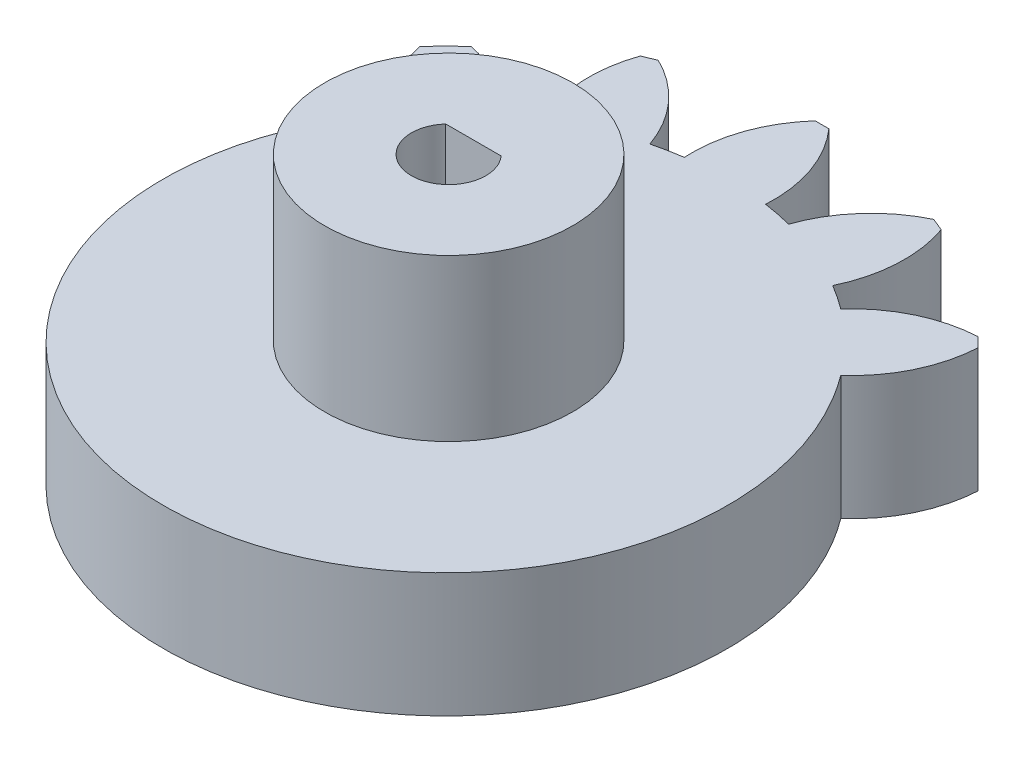
SolidWorks part; units mm, degrees
material "3D printed plastic"
ref_plane "Front Plane" through (0, 0, 0) normal (0, 0, 1) x (1, 0, 0)
ref_plane "Top Plane" through (0, 0, 0) normal (0, 1, 0) x (1, 0, 0)
ref_plane "Right Plane" through (0, 0, 0) normal (1, 0, 0) x (0, 0, -1)
sketch "Sketch1" plane through (0, 0, 0) normal (0, 1, 0) x (1, 0, 0)
  line L0 (0, 12) -> (0, 11.625) construction
  line L1 (0, 11.625) -> (0, 11.25) construction
  line L2 (0, 11.25) -> (0, 10.875) construction
  line L3 (0, 10.875) -> (0, 10.5) construction
  line L4 (0, 10.5) -> (0, 10.125) construction
  line L5 (0, 12) -> (0, 12.375) construction
  line L6 (0, 12.375) -> (0, 12.75) construction
  line L7 (0, 12.75) -> (0, 13.125) construction
  line L8 (0, 13.125) -> (0, 13.5) construction
  line L9 (-2.6337, 13.2406) -> (0, 0) construction
  line L10 (0, 0) -> (2.6337, 13.2406) construction
  line L11 (-2.3411, 11.7694) -> (-1.1762, 11.9422) construction
  line L12 (-1.1762, 11.9422) -> (0, 12) construction
  line L13 (0, 12) -> (1.1762, 11.9422) construction
  line L14 (1.1762, 11.9422) -> (2.3411, 11.7694) construction
  line L15 (-3.3343, 10.3005) -> (3.3343, 10.3005) construction
  line L16 (-1.1762, 11.9422) -> (3.3343, 10.3005) construction
  line L17 (-1.9753, 9.9305) -> (0, 0)
  line L18 (0, 0) -> (1.9753, 9.9305)
  arc A0 (2.6337, 13.2406) -> (-2.6337, 13.2406) centre (0, 0) ccw construction
  arc A1 (1.9753, 9.9305) -> (1.4575, 10.0196) centre (0, 0) ccw
  arc A2 (2.3411, 11.7694) -> (1.1762, 11.9422) centre (0, 0) ccw construction
  arc A3 (-0.2459, 13.4978) -> (-1.4575, 10.0196) centre (3.3343, 10.3005) ccw
  arc A4 (0.2459, 13.4978) -> (1.4575, 10.0196) centre (-3.3343, 10.3005) cw
  arc A5 (0, 12) -> (-1.1762, 11.9422) centre (0, 0) ccw construction
  arc A6 (-1.1762, 11.9422) -> (-2.3411, 11.7694) centre (0, 0) ccw construction
  arc A7 (0, 12) -> (1.1762, 11.9422) centre (0, 0) cw construction
  arc A8 (-1.4575, 10.0196) -> (-1.9753, 9.9305) centre (0, 0) ccw
  arc A9 (-1.4575, 10.0196) -> (1.4575, 10.0196) centre (0, 0) cw construction
  arc A10 (-0.2459, 13.4978) -> (0.2459, 13.4978) centre (0, 0) cw
  dimension "D1" = 24
  dimension "D4" = 4.8
  dimension "D2" = 1.5
  dimension "D3" = 22.5
  dimension "D5" = 70
sketch "Sketch2" plane through (0, 0, 0) normal (1, 0, 0) x (0, 0, -1)
  line L0 (0, 0) -> (0, 5)
  dimension "D1" = 5
sweep "Sweep1" add profiles "Sketch1" path "Sketch2"
ref_axis "Axis1" through (0, 5.25, 0) along (0, -1, 0)
pattern_circular "CirPattern3" count 16 over 360 about axis through (0, 5.25, 0) along (0, -1, 0) of "Sweep1"
sketch "Sketch3" plane through (0, 5, 0) normal (0, 1, 0) x (1, 0, 0)
  line L0 (11.5862, 6.9289) -> (8.6897, 5.1967)
  line L1 (-8.6991, 5.1808) -> (-11.7447, 6.6568)
  arc A0 (-8.6991, 5.1808) -> (8.6897, 5.1967) centre (0, 0) ccw
  arc A1 (-11.7447, 6.6568) -> (11.5862, 6.9289) centre (0, 0) ccw
  arc A2 (12.3762, 5.3925) -> (8.6991, 5.1808) centre (10.7924, 0.8613) ccw construction
  arc A5 (-8.6991, 5.1808) -> (-12.3762, 5.3925) centre (-10.7924, 0.8613) ccw construction
extrude "Cut-Extrude1" cut sketch "Sketch3" against normal through all
sketch "Sketch4" plane through (0, 5, 0) normal (0, 1, 0) x (1, 0, 0)
  line L0 (-9.6375, 8.7246) -> (-9.7556, 9.3316)
  line L1 (-8.7246, 9.6375) -> (-9.3316, 9.7556)
  arc A0 (-9.3316, 9.7556) -> (-9.7556, 9.3316) centre (0, 0) ccw
  arc A1 (-8.7246, 9.6375) -> (-9.6375, 8.7246) centre (0, 0) ccw
  arc A2 (-9.7182, 9.3705) -> (-8.1155, 6.0543) centre (-4.9258, 9.6413) ccw construction
  arc A3 (-6.0543, 8.1155) -> (-9.3705, 9.7182) centre (-9.6413, 4.9258) ccw construction
  dimension "D1" = 0.5
extrude "Cut-Extrude2" cut sketch "Sketch4" against normal through all
scale "Scale1" scale about centroid uniform scaling no x scale factor 1.125 y scale factor 1 z scale factor 1.125
sketch "Sketch6" plane through (0, 5, 0) normal (0, 1, 0) x (1, 0, 0)
  line L0 (0, 0) -> (-5.6921, 5.6214) construction
  line L1 (-5.6921, 5.6214) -> (-10.3429, 10.2145) construction
  circle A0 centre (-5.6921, 5.6214) radius 0.75
  arc A1 (-9.8166, 10.7152) -> (-10.8437, 9.6882) centre (-0.0015, -0.127) ccw construction
  dimension "D1" = 1.5
  dimension "D2" = 8
extrude "Cut-Extrude4" cut sketch "Sketch6" against normal blind 0.5
ref_plane "Plane1" through (0, 2.5, 0) normal (0, -1, 0) x (-1, 0, 0)
mirror "Mirror1" about plane through (0, 2.5, 0) normal (0, -1, 0) of "Cut-Extrude4"
sketch "Sketch5" plane through (0, 5, 0) normal (0, 1, 0) x (1, 0, 0)
  line L0 (-1.118, 1) -> (1.118, 1)
  arc A0 (-1.118, 1) -> (1.118, 1) centre (0, 0) ccw
  dimension "D1" = 1.5
  dimension "D2" = 1
extrude "Cut-Extrude3" cut sketch "Sketch5" against normal through all
sketch "Sketch7" plane through (0, 5, 0) normal (0, 1, 0) x (1, 0, 0)
  line L0 (1.118, 1) -> (-1.118, 1) construction
  line L1 (1.118, 1) -> (-1.118, 1)
  circle A0 centre (0, 0) radius 5
  arc A1 (-1.118, 1) -> (1.118, 1) centre (0, 0) ccw construction
  arc A2 (-1.118, 1) -> (1.118, 1) centre (0, 0) ccw
  dimension "D1" = 10
extrude "Boss-Extrude1" add sketch "Sketch7" along normal blind 6.5
